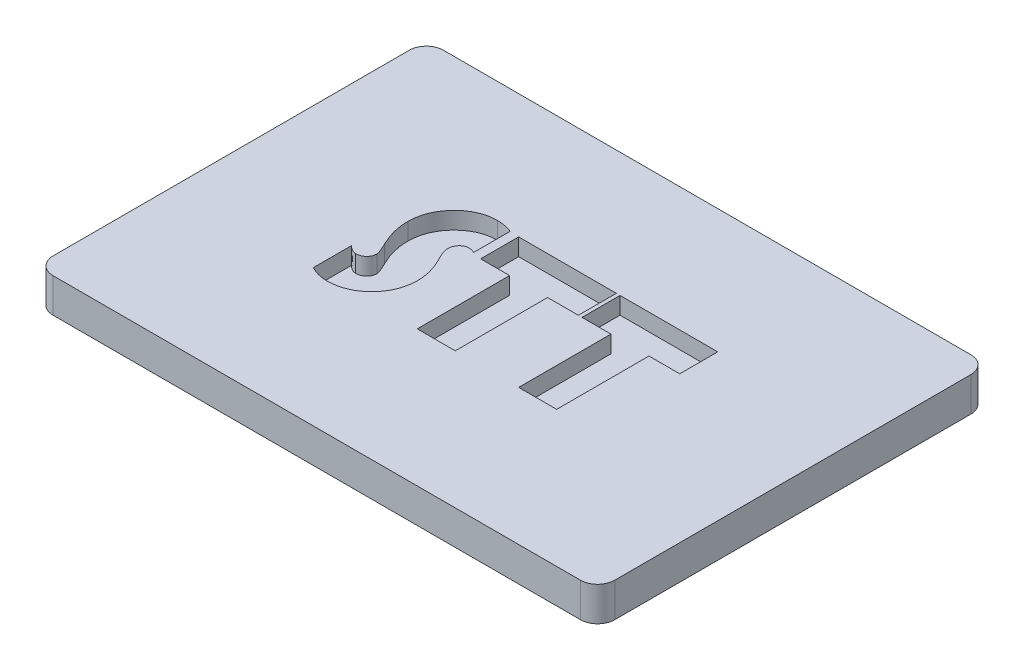
SolidWorks part; units mm, degrees
ref_plane "Front Plane" through (0, 0, 0) normal (0, 0, 1) x (1, 0, 0)
ref_plane "Top Plane" through (0, 0, 0) normal (0, 1, 0) x (1, 0, 0)
ref_plane "Right Plane" through (0, 0, 0) normal (1, 0, 0) x (0, 0, -1)
sketch "Sketch1" plane through (0, 0, 0) normal (0, 1, 0) x (1, 0, 0)
  line L1 (0, 0) -> (32.8, 0)
  line L2 (0, 0) -> (0, 22.8)
  line L3 (0, 22.8) -> (32.8, 22.8)
  line L4 (32.8, 0) -> (32.8, 22.8)
  dimension "D1" = 22.8
  dimension "D2" = 32.8
extrude "Boss-Extrude1" add sketch "Sketch1" along normal blind 2
fillet "Fillet1" radius 1 4 edges at (0, 1, -22.8) (32.8, 1, -22.8) (32.8, 1, 0) (0, 1, 0)
sketch "Sketch2" plane through (0, 2, 0) normal (0, 1, 0) x (1, 0, 0)
  text T0 "STT" font "Bauhaus 93" height in points 24
extrude "Cut-Extrude1" cut sketch "Sketch2" against normal blind 1
